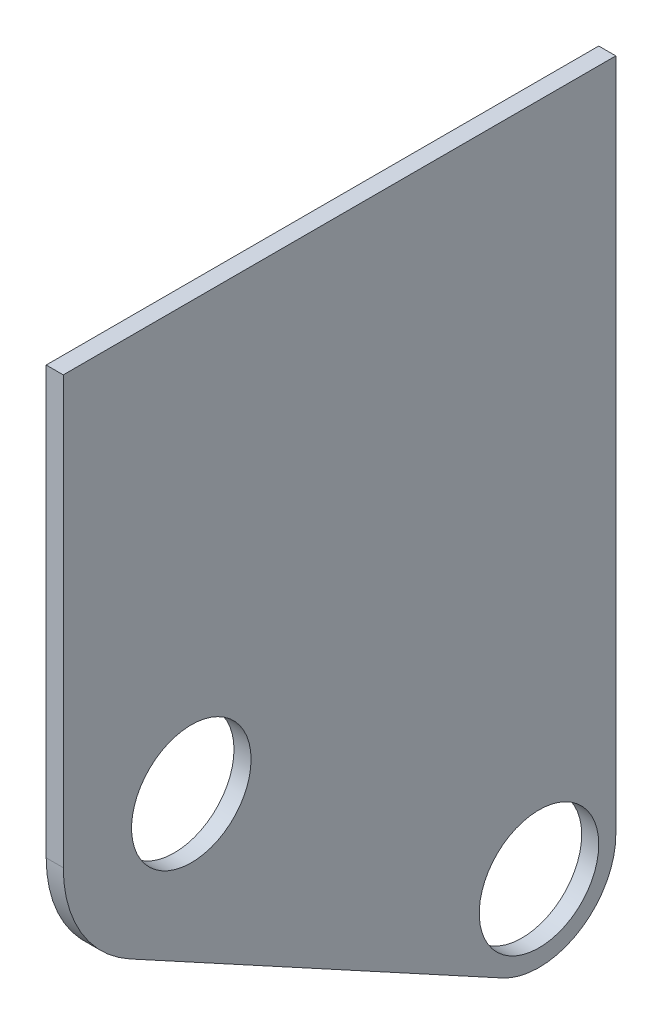
SolidWorks part; units mm, degrees
material "6061-T6 (SS)"
ref_plane "Front" through (0, 0, 0) normal (0, 0, 1) x (1, 0, 0)
ref_plane "Top" through (0, 0, 0) normal (0, 1, 0) x (1, 0, 0)
ref_plane "Right" through (0, 0, 0) normal (1, 0, 0) x (0, 0, -1)
sketch "Sketch2" plane through (0, 0, 0) normal (1, 0, 0) x (0, 0, -1)
  line L0 (51.3801, 0) -> (-51.3801, 0)
  line L1 (-51.3801, 0) -> (-51.3801, -79.375)
  line L2 (-38.9513, -100.2902) -> (30.2624, -137.9616)
  line L3 (51.3801, -125.4125) -> (51.3801, 0)
  line L4 (215.629, -146.05) -> (-215.629, -146.05) construction
  line L5 (-51.3801, -50.8) -> (51.3801, -50.8) construction
  circle A0 centre (-27.5676, -79.375) radius 11.1125
  circle A1 centre (37.0926, -125.4125) radius 11.1125
  circle A2 centre (-27.5676, -79.375) radius 28.575 construction
  circle A3 centre (37.0926, -125.4125) radius 12.7 construction
  arc A4 (-51.3801, -79.375) -> (-38.9513, -100.2902) centre (-27.5676, -79.375) ccw
  arc A5 (30.2624, -137.9616) -> (51.3801, -125.4125) centre (37.0926, -125.4125) ccw
  point P4 (0, 0)
  point P17 (0, -146.05)
  point P19 (-17.2889, -63.5)
  point P20 (0, 0)
  point P21 (35.3766, -114.0125)
  dimension "D1" = 22.225
  dimension "D2" = 57.15
  dimension "D3" = 25.4
  dimension "D4" = 38.1
  dimension "D5" = 3.175
  dimension "D6" = 12.7
  dimension "D7" = 6.35
  dimension "D8" = 38.1
  dimension "D9" = 50.8
  dimension "D10" = 95.25
extrude "Boss-Extrude1" add sketch "Sketch2" along normal blind 3.175
